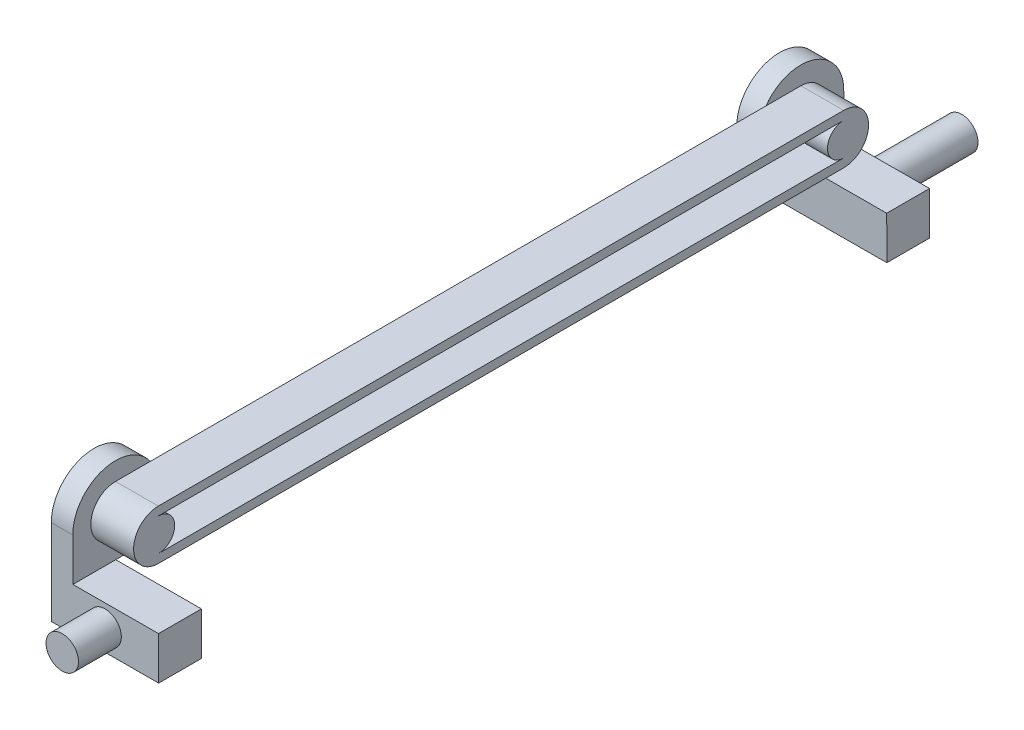
SolidWorks part; units mm, degrees
ref_plane "Front Plane" through (0, 0, 0) normal (0, 0, 1) x (1, 0, 0)
ref_plane "Top Plane" through (0, 0, 0) normal (0, 1, 0) x (1, 0, 0)
ref_plane "Right Plane" through (0, 0, 0) normal (1, 0, 0) x (0, 0, -1)
sketch "Sketch1" plane through (0, 0, 0) normal (0, 0, 1) x (1, 0, 0)
  line L0 (354.7291, 111.8807) -> (355.373, 111.8807) construction
  line L1 (355.3607, 115.6778) -> (161.3617, 115.0491) construction
  circle A0 centre (354.7291, 111.8807) radius 3.795
  dimension "D1" = 7.59
extrude "Boss-Extrude1" add sketch "Sketch1" along normal mid plane 20
sketch "Sketch3" plane through (0, 0, 10) normal (0, 0, 1) x (1, 0, 0)
  line L0 (355.3607, 115.6778) -> (161.3617, 115.0491) construction
  line L1 (367.2129, 116.9212) -> (342.2129, 116.8402)
  line L2 (367.2129, 116.9212) -> (367.2453, 106.9212)
  line L3 (367.2453, 106.9212) -> (342.2453, 106.8402)
  line L4 (342.2129, 116.8402) -> (342.2453, 106.8402)
  line L5 (367.2129, 116.9212) -> (342.2453, 106.8402) construction
  line L6 (367.2453, 106.9212) -> (342.2129, 116.8402) construction
  line L7 (336.3871, 92.1703) -> (336.2597, 131.4676) construction
  circle A0 centre (354.7291, 111.8807) radius 3.795 construction
  point P0 (354.7291, 111.8807)
  dimension "D1" = 25
  dimension "D2" = 10
extrude "Boss-Extrude2" add sketch "Sketch3" along normal blind 180
sketch "Sketch4" plane through (0, 0, 190) normal (0, 0, 1) x (1, 0, 0)
  circle A0 centre (354.7291, 111.8807) radius 3.795
  circle A1 centre (354.7291, 111.8807) radius 3.795 construction
extrude "Boss-Extrude3" add sketch "Sketch4" along normal blind 10
ref_plane "Plane2" through (0, 0, 100) normal (0, 0, 1) x (1, 0, 0)
sketch "Sketch7" plane through (342.5879, 1.1102, 0) normal (-1, -0.0032, 0) x (0, 0, 1)
  line L0 (10, 115.7306) -> (10, 125.7306)
  line L1 (30, 125.7306) -> (30, 115.7306)
  line L2 (190, 115.7306) -> (10, 115.7306) construction
  line L3 (30, 115.7306) -> (10, 115.7306)
  arc A0 (10, 125.7306) -> (30, 125.7306) centre (20, 125.7306) cw
  circle A1 centre (20, 125.7306) radius 3.795
  dimension "D1" = 10
  dimension "D2" = 7.59
  dimension "D3" = 10
extrude "Boss-Extrude6" add sketch "Sketch7" against normal blind 5
extrude "Boss-Extrude7" add sketch "Sketch7<2>" against normal blind 15 contours A1 region at (342.1805, 126.8401, 20)
sketch "Sketch7<2>" plane through (342.5879, 1.1102, 0) normal (-1, -0.0032, 0) x (0, 0, 1) same geometry as "Sketch7"
mirror "Mirror2" about plane through (0, 0, 100) normal (0, 0, 1) of "Boss-Extrude7", "Boss-Extrude6"
sketch "Sketch8" plane through (347.5879, 1.1264, 0) normal (1, 0.0032, 0) x (0, 0, -1)
  line L0 (-180, 129.5256) -> (-20, 129.5256)
  line L1 (-20, 121.9356) -> (-180, 121.9356)
  line L2 (-180, 131.5256) -> (-20, 131.5256)
  line L3 (-20, 119.9356) -> (-180, 119.9356)
  circle A0 centre (-180, 125.7306) radius 3.795 construction
  circle A1 centre (-20, 125.7306) radius 3.795 construction
  arc A2 (-180, 129.5256) -> (-180, 121.9356) centre (-180, 125.7306) ccw
  arc A3 (-20, 121.9356) -> (-20, 129.5256) centre (-20, 125.7306) ccw
  arc A4 (-20, 119.9356) -> (-20, 131.5256) centre (-20, 125.7306) ccw
  arc A5 (-180, 131.5256) -> (-180, 119.9356) centre (-180, 125.7306) ccw
  dimension "D1" = 2
extrude "Boss-Extrude8" add sketch "Sketch8" along normal blind 10
sketch "Sketch9" plane through (-0.375, 115.73, 0) normal (-0.0032, 1, 0) x (1, 0.0032, 0)
  line L0 (367.5899, -20) -> (-112.114, -20)
  line L1 (367.5899, -190) -> (367.5899, -10) construction
  line L2 (-112.114, -20) -> (-112.114, -180)
  line L3 (-112.114, -180) -> (367.5899, -180)
  line L4 (367.5899, -10) -> (347.5897, -10) construction
  line L5 (367.5899, -190) -> (347.5897, -190) construction
  line L8 (367.5899, -20) -> (367.5899, -180)
  dimension "D1" = 10
  dimension "D2" = 10
extrude "Cut-Extrude1" cut sketch "Sketch9" against normal through all
